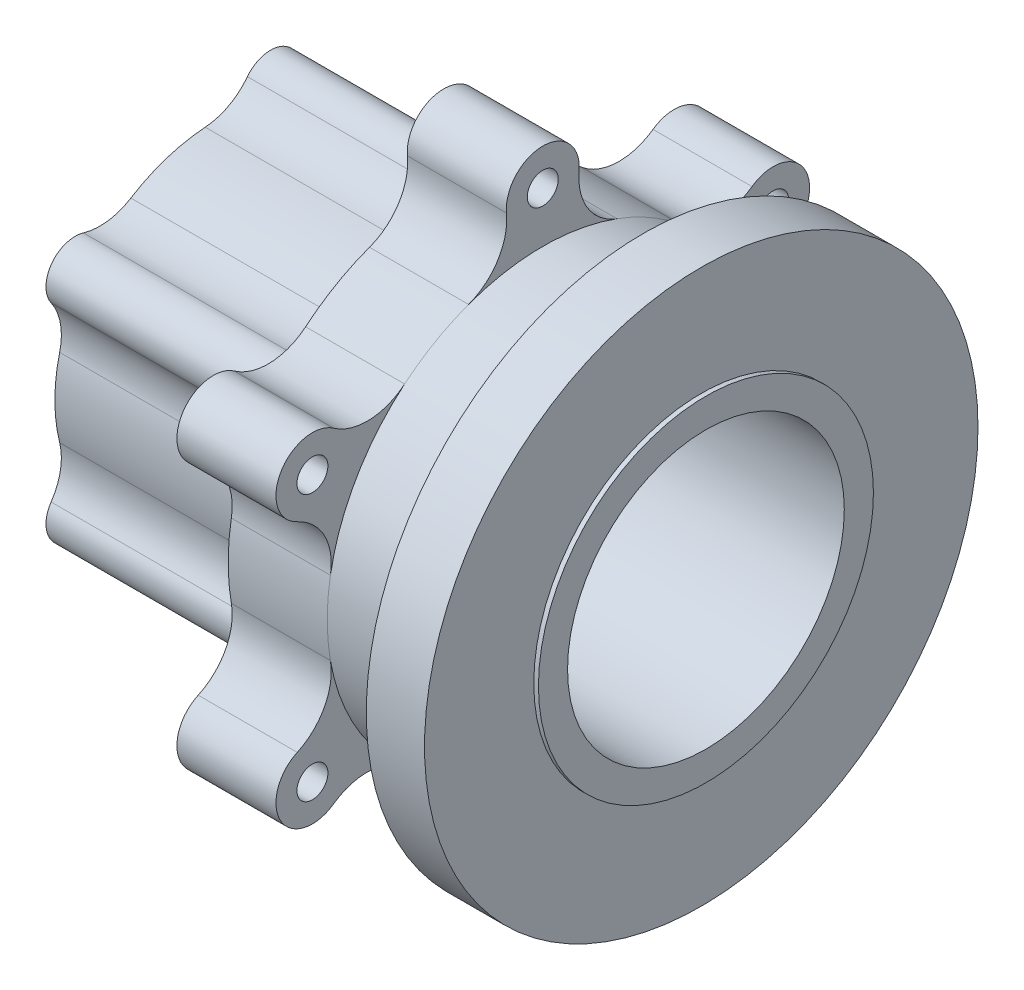
SolidWorks part; units mm, degrees
ref_plane "Front Plane" through (0, 0, 0) normal (1, 0, 0) x (0, 1, 0)
ref_plane "Top Plane" through (0, 0, 0) normal (0, 0, 1) x (0, 1, 0)
ref_plane "Right Plane" through (0, 0, 0) normal (0, 1, 0) x (-1, 0, 0)
sketch "Sketch1" plane through (0, 0, 0) normal (0, 1, 0) x (-1, 0, 0)
  line L0 (0, 68.99) -> (6.35, 68.99)
  line L1 (0, 0) -> (71.12, 0)
  line L2 (0, 0) -> (0, 157.48)
  line L3 (0, 157.48) -> (71.12, 157.48) construction
  line L4 (71.12, 0) -> (71.12, 157.48)
  line L5 (6.35, 68.99) -> (6.35, 149.987)
  line L6 (6.35, 149.987) -> (13.843, 157.48)
  line L7 (63.627, 157.48) -> (71.12, 149.987)
  line L8 (-21.844, 60.325) -> (-21.844, 36.5125)
  line L9 (0, 0) -> (-20.32, 0)
  line L10 (0, 0) -> (0, 46.99)
  line L11 (0, 46.99) -> (-20.32, 46.99)
  line L12 (-20.32, 0) -> (-20.32, 46.99)
  line L13 (71.12, 0) -> (83.82, 0) construction
  line L14 (71.12, 0) -> (71.12, 14.9987) construction
  line L15 (71.12, 14.9987) -> (83.82, 14.9987) construction
  line L16 (83.82, 0) -> (83.82, 14.9987) construction
  line L17 (83.82, 0) -> (96.52, 0) construction
  line L18 (83.82, 0) -> (83.82, 24.13) construction
  line L19 (83.82, 24.13) -> (96.52, 24.13) construction
  line L20 (96.52, 0) -> (96.52, 24.13) construction
  line L21 (-20.32, 0) -> (-35.56, 0)
  line L22 (-20.32, 0) -> (-20.32, 36.5125)
  line L23 (-20.32, 36.5125) -> (-35.56, 36.5125)
  line L24 (-35.56, 0) -> (-35.56, 36.5125)
  line L25 (-21.844, 36.5125) -> (-34.544, 36.5125)
  line L26 (-34.544, 36.5125) -> (-34.544, 60.325)
  line L27 (-34.544, 60.325) -> (-21.844, 60.325)
  line L28 (6.35, 68.99) -> (71.12, 68.99)
  dimension "D1" = 157.48
  dimension "D2" = 71.12
  dimension "D3" = 12.7
  dimension "D4" = 12.7
  dimension "D5" = 14.9987
  dimension "D6" = 24.13
  dimension "D7" = 20.32
  dimension "D8" = 45
  dimension "D9" = 45
  dimension "D10" = 6.35
  dimension "D11" = 46.99
  dimension "D13" = 36.5125
  dimension "D14" = 132.08
  dimension "D12" = 49.784
  dimension "D16" = 60.325
  dimension "D17" = 12.7
  dimension "D18" = 36.5125
  dimension "D19" = 68.99
  dimension "D15" = 1.016
revolve "Revolve1" add sketch "Sketch1" angle 360 about L1 region at (-35.56, 0, 34.495) region at (10.16, 0, 23.495) region at (27.94, 0, 18.2562)
revolve "Revolve2" add sketch "Sketch1<3>" angle 360 about L1 region at (28.194, 0, 48.4187)
sketch "Sketch1<3>" plane through (0, 0, 0) normal (0, 1, 0) x (-1, 0, 0) same geometry as "Sketch1"
sketch "Sketch2" plane through (-71.12, 0, 0) normal (-1, 0, 0) x (0, -1, 0)
  line L1 (0, -38.1) -> (36.2353, -11.7735)
  line L2 (36.2353, -11.7735) -> (22.3946, 30.8235)
  line L3 (22.3946, 30.8235) -> (-22.3946, 30.8235)
  line L4 (-22.3946, 30.8235) -> (-36.2353, -11.7735)
  line L5 (-36.2353, -11.7735) -> (0, -38.1)
  circle A0 centre (0, 0) radius 38.1
  circle A1 centre (0, 0) radius 68.99
  circle A3 centre (0, 0) radius 30.8235 construction
  circle A5 centre (0, 0) radius 68.99
  dimension "D2" = 76.2
  dimension "D1" = 0
sketch "Sketch3" plane through (-71.12, 0, 0) normal (-1, 0, 0) x (0, -1, 0)
  circle A0 centre (-22.3946, 30.8235) radius 3.3734
  circle A1 centre (22.3946, 30.8235) radius 3.3734
  circle A2 centre (36.2353, -11.7735) radius 3.3734
  circle A3 centre (0, -38.1) radius 3.3734
  circle A4 centre (-36.2353, -11.7735) radius 3.3734
  point P0 (-36.2353, -11.7735)
  point P2 (0, -38.1)
  point P4 (36.2353, -11.7735)
  point P6 (22.3946, 30.8235)
  point P8 (-22.3946, 30.8235)
  dimension "D1" = 6.7469
extrude "Cut-Extrude1" cut sketch "Sketch3" against normal blind 13.97
sketch "Sketch4" plane through (0, 0, 0) normal (1, 0, 0) x (0, 1, 0)
  line L0 (28.995, -50.2208) -> (57.99, 0)
  line L1 (57.99, 0) -> (28.995, 50.2208)
  line L2 (28.995, 50.2208) -> (-28.995, 50.2208)
  line L3 (-28.995, 50.2208) -> (-57.99, 0)
  line L4 (-57.99, 0) -> (-28.995, -50.2208)
  line L5 (-28.995, -50.2208) -> (28.995, -50.2208)
  circle A0 centre (0, 0) radius 50.2208 construction
  circle A1 centre (0, 0) radius 68.99
  circle A2 centre (0, 0) radius 68.99
  circle A3 centre (28.995, 50.2208) radius 3.3734
  dimension "D3" = 6.7469
  dimension "D2" = 115.98
  dimension "D1" = 0
sketch "Sketch5" plane through (0, 0, 0) normal (1, 0, 0) x (0, 1, 0)
  circle A0 centre (28.995, 50.2208) radius 3.3734 construction
  circle A1 centre (28.995, 50.2208) radius 3.3734
  circle A2 centre (-28.995, 50.2208) radius 3.3734
  circle A3 centre (-57.99, 0) radius 3.3734
  circle A4 centre (-28.995, -50.2208) radius 3.3734
  circle A5 centre (28.995, -50.2208) radius 3.3734
  circle A6 centre (57.99, 0) radius 3.3734
  point P0 (28.995, -50.2208)
  point P2 (57.99, 0)
  point P4 (28.995, 50.2208)
  point P9 (-28.995, -50.2208)
  point P11 (-57.99, 0)
  point P13 (-28.995, 50.2208)
extrude "Cut-Extrude2" cut sketch "Sketch5" against normal blind 13.97
sketch "Sketch10" plane through (0, 0, 0) normal (1, 0, 0) x (0, 1, 0)
  line L0 (-28.995, 50.2208) -> (0, 0) construction
  circle A0 centre (0, -38.1) radius 3.3734 construction
  circle A1 centre (-36.2353, -11.7735) radius 3.3734 construction
  circle A2 centre (-22.3946, 30.8235) radius 3.3734 construction
  circle A3 centre (36.2353, -11.7735) radius 3.3734 construction
  circle A4 centre (22.3946, 30.8235) radius 3.3734 construction
  circle A5 centre (0, -38.1) radius 3.3734
  circle A6 centre (-36.2353, -11.7735) radius 3.3734
  circle A7 centre (-22.3946, 30.8235) radius 3.3734
  circle A8 centre (36.2353, -11.7735) radius 3.3734
  circle A9 centre (22.3946, 30.8235) radius 3.3734
  circle A10 centre (57.99, 0) radius 3.3734 construction
  circle A11 centre (28.995, -50.2208) radius 3.3734 construction
  circle A12 centre (-28.995, -50.2208) radius 3.3734 construction
  circle A13 centre (-57.99, 0) radius 3.3734 construction
  circle A14 centre (-28.995, 50.2208) radius 3.3734 construction
  circle A15 centre (28.995, 50.2208) radius 3.3734 construction
  circle A16 centre (57.99, 0) radius 3.3734
  circle A17 centre (28.995, -50.2208) radius 3.3734
  circle A18 centre (-28.995, -50.2208) radius 3.3734
  circle A19 centre (-57.99, 0) radius 3.3734
  circle A20 centre (-28.995, 50.2208) radius 3.3734
  circle A21 centre (28.995, 50.2208) radius 3.3734
  circle A22 centre (0, 0) radius 68.99 construction
  circle A23 centre (0, 0) radius 46.99 construction
  circle A24 centre (0, 0) radius 68.99
  circle A25 centre (0, 0) radius 46.99
  circle A26 centre (-28.995, 50.2208) radius 7.9454
  arc A27 (-35.4699, 45.6159) -> (-36.0706, 30.1159) centre (-45.8195, 38.2554) cw
  arc A28 (-21.7696, 53.5258) -> (-8.0458, 46.2961) centre (-10.2204, 58.8085) ccw
  arc A29 (35.4699, 45.6159) -> (36.0706, 30.1159) centre (45.8195, 38.2554) ccw
  circle A30 centre (28.995, 50.2208) radius 7.9454
  arc A31 (21.7696, 53.5258) -> (8.0458, 46.2961) centre (10.2204, 58.8085) cw
  arc A32 (57.2395, -7.9099) -> (44.1165, -16.1801) centre (56.0399, -20.5531) ccw
  circle A33 centre (57.99, 0) radius 7.9454
  arc A34 (57.2395, 7.9099) -> (44.1165, 16.1801) centre (56.0399, 20.5531) cw
  arc A35 (21.7696, -53.5258) -> (8.0458, -46.2961) centre (10.2204, -58.8085) ccw
  circle A36 centre (28.995, -50.2208) radius 7.9454
  arc A37 (35.4699, -45.6159) -> (36.0706, -30.1159) centre (45.8195, -38.2554) cw
  arc A38 (-35.4699, -45.6159) -> (-36.0706, -30.1159) centre (-45.8195, -38.2554) ccw
  circle A39 centre (-28.995, -50.2208) radius 7.9454
  arc A40 (-21.7696, -53.5258) -> (-8.0458, -46.2961) centre (-10.2204, -58.8085) cw
  arc A41 (-57.2395, 7.9099) -> (-44.1165, 16.1801) centre (-56.0399, 20.5531) ccw
  circle A42 centre (-57.99, 0) radius 7.9454
  arc A43 (-57.2395, -7.9099) -> (-44.1165, -16.1801) centre (-56.0399, -20.5531) cw
  point P87 (0, 0)
  circle M12 centre (0, 0) radius 68.99
  circle M13 centre (0, 0) radius 46.99
  dimension "D1" = 4.572
  dimension "D2" = 12.7
  dimension "D3" = 6
extrude "Cut-Extrude3" cut sketch "Sketch10" against normal through all contours A43 A42 A41 A27 A26 A28 A25 A31 A30 A29 A34 A33 A32 A37 A36 A35 A40 A39 A38 M12 M13 region at (0, -67.0387, 0)
ref_plane "Plane1" through (-21.59, 0, 0) normal (1, 0, 0) x (0, 0, -1)
sketch "Sketch12" plane through (-21.59, 0, 0) normal (1, 0, 0) x (0, 0, -1)
  circle A0 centre (0, 0) radius 46.99 construction
  circle A1 centre (0, 0) radius 46.99
  circle A2 centre (0, 0) radius 65.9354
  arc A3 (-7.9099, -57.2395) -> (7.9099, -57.2395) centre (0, -57.99) ccw construction
extrude "Cut-Extrude6" cut sketch "Sketch12" against normal through all
sketch "Sketch13" plane through (-71.12, 0, 0) normal (-1, 0, 0) x (0, -1, 0)
  line L0 (0, 0) -> (0, 30.1625) construction
  line L1 (0, 0) -> (-26.1271, 35.9608) construction
  circle A0 centre (0, 0) radius 36.5125 construction
  circle A1 centre (0, 0) radius 36.5125 construction
  circle A2 centre (0, 0) radius 46.99 construction
  circle A3 centre (22.3946, 30.8235) radius 3.3734 construction
  circle A4 centre (-22.3946, 30.8235) radius 3.3734 construction
  circle A5 centre (0, 0) radius 46.99
  circle A6 centre (22.3946, 30.8235) radius 3.3734
  circle A7 centre (-22.3946, 30.8235) radius 3.3734
  circle A8 centre (0, 0) radius 30.1625
  circle A9 centre (0, 0) radius 35.2425
  circle A10 centre (-22.3946, 30.8235) radius 6.35
  arc A11 (-18.7957, 36.0552) -> (-8.5256, 34.1957) centre (-11.5979, 46.5185) ccw
  circle A12 centre (22.3946, 30.8235) radius 6.35
  arc A13 (18.7957, 36.0552) -> (8.5256, 34.1957) centre (11.5979, 46.5185) cw
  arc A14 (40.0987, -6.7341) -> (35.1566, 2.4588) centre (47.8257, 3.3448) cw
  arc A15 (28.4823, 29.0174) -> (29.8875, 18.6754) centre (40.6578, 25.4052) ccw
  circle A16 centre (36.2353, -11.7735) radius 6.35
  arc A17 (5.9867, -40.2171) -> (13.2024, -32.6761) centre (17.96, -44.4513) cw
  arc A18 (36.3988, -18.1214) -> (26.9971, -22.6537) centre (36.7258, -30.8172) ccw
  circle A19 centre (0, -38.1) radius 6.35
  arc A20 (-36.3988, -18.1214) -> (-26.9971, -22.6537) centre (-36.7258, -30.8172) cw
  arc A21 (-5.9867, -40.2171) -> (-13.2024, -32.6761) centre (-17.96, -44.4513) ccw
  circle A22 centre (-36.2353, -11.7735) radius 6.35
  arc A23 (-28.4823, 29.0174) -> (-29.8875, 18.6754) centre (-40.6578, 25.4052) cw
  arc A24 (-40.0987, -6.7341) -> (-35.1566, 2.4588) centre (-47.8257, 3.3448) ccw
  circle A25 centre (-22.3946, 30.8235) radius 6.35
  point P57 (0, 0)
  circle M8 centre (0, 0) radius 46.99
  dimension "D1" = 6.35
  dimension "D2" = 5.08
  dimension "D3" = 44.45
  dimension "D4" = 12.7
  dimension "D5" = 5
extrude "Cut-Extrude7" cut sketch "Sketch13" against normal up to surface (49.53 mm away) contours A22 A24 A9 A23 A10 A11 A13 A12 A15 A14 A16 A18 A17 A19 A21 A20 M8 region at (-71.12, 45.6609, 0) up to face at (-21.59, 26.4329, 45.783)
extrude "Cut-Extrude8" cut sketch "Sketch13<3>" against normal through all contours A8 region at (-71.12, 0, 0)
sketch "Sketch13<3>" plane through (-71.12, 0, 0) normal (-1, 0, 0) x (0, -1, 0) same geometry as "Sketch13"
ref_plane "Plane2" through (0, 0, 0) normal (1, 0, 0) x (0, 0, -1)
split line "Split Line7"
equation "\"D9@Sketch1\"=\"D8@Sketch1\""
equation "\"D19@Sketch1\"=115.98mm-\"D11@Sketch1\""
